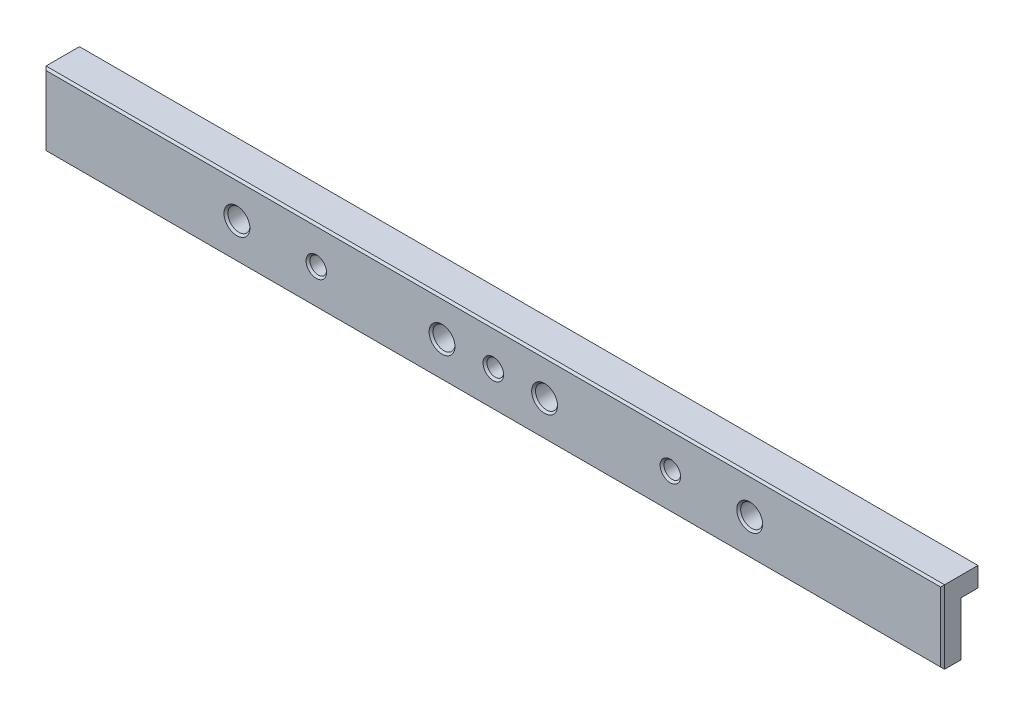
SolidWorks part; units mm, degrees
ref_plane "Front Plane" through (0, 0, 0) normal (0, 0, 1) x (1, 0, 0)
ref_plane "Top Plane" through (0, 0, 0) normal (0, 1, 0) x (1, 0, 0)
ref_plane "Right Plane" through (0, 0, 0) normal (1, 0, 0) x (0, 0, -1)
sketch "Sketch1" plane through (0, 0, 0) normal (0, 0, 1) x (1, 0, 0)
  line L0 (0, 7.5) -> (0, 0) construction
  line L1 (92, 7.5) -> (-92, 7.5)
  line L2 (92, 7.5) -> (92, 3.5)
  line L3 (92, -7.5) -> (-92, -7.5)
  line L4 (-92, 7.5) -> (-92, 3.5)
  line L5 (92, 3.5) -> (-92, 3.5)
  line L6 (-92, 3.5) -> (-92, -7.5)
  line L7 (92, 3.5) -> (92, -7.5)
  line L8 (0, 0) -> (0, -7.5) construction
  dimension "D1" = 92
  dimension "D2" = 7.5
  dimension "D3" = 4
extrude "Boss-Extrude1" add sketch "Sketch1" against normal blind 7.25 contours L7 L5 L6 L3 | L1 L0 L5 L2 | L0 L1 L4 L5 region at (46, 5.5, 0) region at (-46, 5.5, 0) region at (0, -2, 0)
extrude "Cut-Extrude1" cut sketch "Sketch1<6>" along normal blind 3.5 from surface contours L7 L5 L6 L3 region at (0, -2, 0) starting at face at (0, 0, -7.25)
sketch "Sketch1<6>" plane through (0, 0, 0) normal (0, 0, 1) x (1, 0, 0) same geometry as "Sketch1"
sketch "Sketch2" plane through (0, 0, 0) normal (0, 0, 1) x (1, 0, 0)
  circle A0 centre (-52.5, 0) radius 2.25
  circle A8 centre (-36.25, 0) radius 1.7
  circle A9 centre (-10.5, 0) radius 2.25
  circle A12 centre (0, 0) radius 1.7
  circle A13 centre (10.5, 0) radius 2.25
  circle A14 centre (36.25, 0) radius 1.7
  circle A15 centre (52.5, 0) radius 2.25
  point P14 (-52.5, 0)
  point P15 (-36.25, 0)
  point P16 (-10.5, 0)
  point P17 (10.5, 0)
  point P18 (36.25, 0)
  point P19 (52.5, 0)
  dimension "D2" = 4.5
  dimension "D1" = 3.4
extrude "Cut-Extrude2" cut sketch "Sketch2" against normal through all both and the other way through all
chamfer "Chamfer1" distance 0.4 angle 45 11 edges at (0, -7.5, 0) (-92, 0, 0) (0, 7.5, 0) (92, 0, 0) (54.75, 0, 0) (37.95, 0, 0) (12.75, 0, 0) (1.7, 0, 0) (-8.25, 0, 0) (-34.55, 0, 0) (-50.25, 0, 0)
